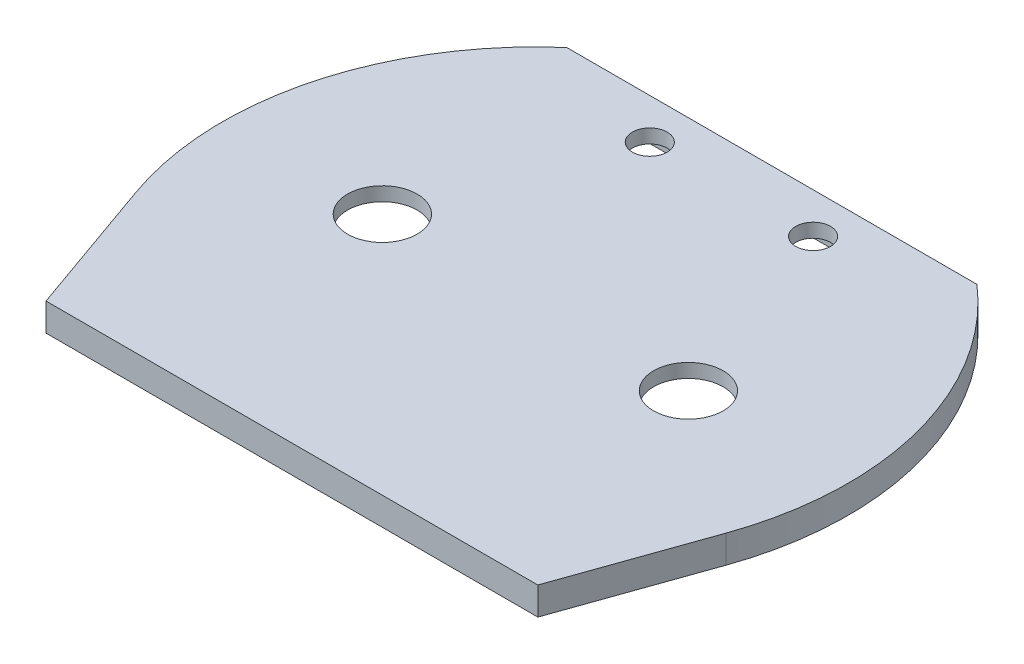
SolidWorks part; units mm, degrees
ref_plane "Front Plane" through (0, 0, 0) normal (0, 0, 1) x (1, 0, 0)
ref_plane "Top Plane" through (0, 0, 0) normal (0, 1, 0) x (1, 0, 0)
ref_plane "Right Plane" through (0, 0, 0) normal (1, 0, 0) x (0, 0, -1)
sketch "Sketch1" plane through (0, 0, 0) normal (0, 1, 0) x (1, 0, 0)
  line L0 (-57.15, 0) -> (57.15, 0) construction
  line L1 (0, 43.18) -> (0, -44.45) construction
  line L2 (27.94, 0) -> (14.909, 35.8023) construction
  line L3 (-27.94, 0) -> (-14.909, 35.8023) construction
  line L5 (-37.4381, 43.18) -> (37.4381, 43.18)
  line L6 (-53.8815, -19.05) -> (-44.9013, -44.45)
  line L7 (-44.9013, -44.45) -> (44.9013, -44.45)
  line L8 (44.9013, -44.45) -> (53.8815, -19.05)
  arc A0 (-37.4381, 43.18) -> (-53.8815, -19.05) centre (0, 0) ccw
  circle A3 centre (27.94, 0) radius 6.35
  circle A4 centre (14.909, 35.8023) radius 3.175
  circle A5 centre (-27.94, 0) radius 6.35
  circle A6 centre (-14.909, 35.8023) radius 3.175
  arc A7 (53.8815, -19.05) -> (37.4381, 43.18) centre (0, 0) ccw
  dimension "D1" = 38.1
  dimension "D4" = 12.7
  dimension "D5" = 6.35
  dimension "D6" = 114.3
  dimension "D2" = 70
  dimension "D3" = 27.94
  dimension "D7" = 43.18
  dimension "D8" = 19.05
  dimension "D9" = 25.4
extrude "Boss-Extrude1" add sketch "Sketch1" along normal blind 5.08
shell "Shell2" thickness 2.54 removed face at (0, 0, 5.9283)
sketch "Sketch3" plane through (0, 0, 0) normal (0, -1, 0) x (1, 0, 0)
  line L0 (-36.478, -40.64) -> (-36.9074, 8.89)
  line L1 (-36.9074, 8.89) -> (36.9074, 8.89)
  line L2 (36.9074, 8.89) -> (36.478, -40.64)
  line L3 (36.478, -40.64) -> (-36.478, -40.64)
  circle A0 centre (-27.94, 0) radius 8.89 construction
  circle A1 centre (27.94, 0) radius 8.89 construction
extrude "Cut-Extrude1" cut sketch "Sketch3" against normal up to surface (2.54 mm away) up to face at (-27.94, 2.54, 8.89)
